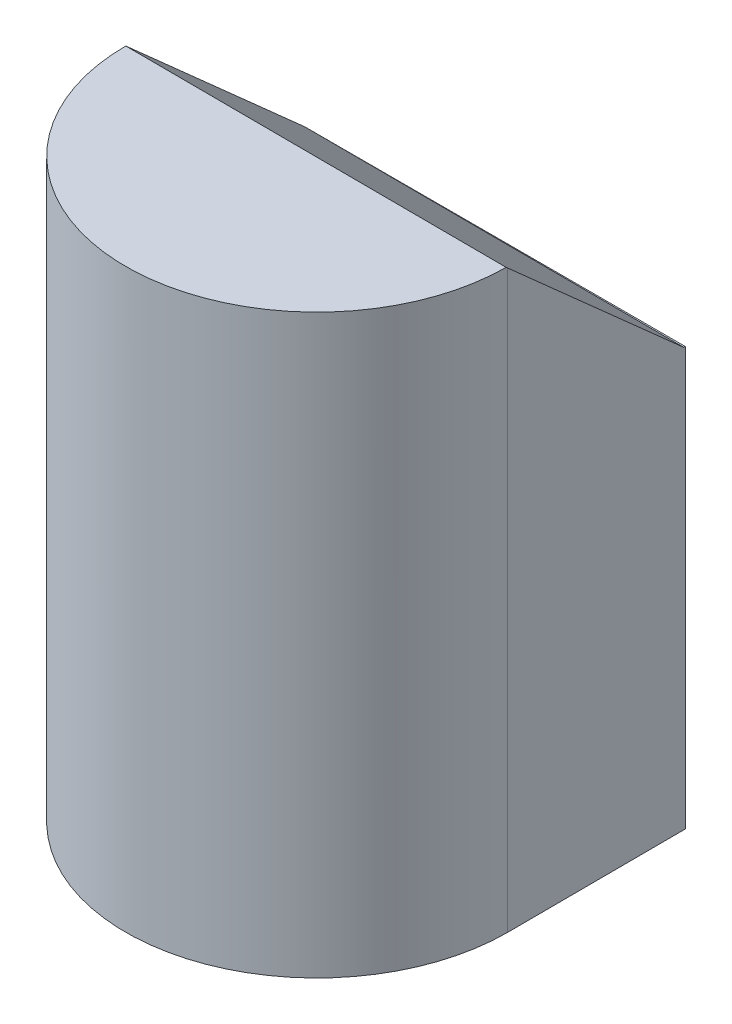
SolidWorks part; units mm, degrees
ref_plane "Front Plane" through (0, 0, 0) normal (0, 0, 1) x (1, 0, 0)
ref_plane "Top Plane" through (0, 0, 0) normal (0, 1, 0) x (1, 0, 0)
ref_plane "Right Plane" through (0, 0, 0) normal (1, 0, 0) x (0, 0, -1)
sketch "Sketch3" plane through (0, 0, 0) normal (0, 1, 0) x (1, 0, 0)
  line L1 (0, 0) -> (0, 270.6759) construction
  line L2 (-54.4068, 0) -> (54.4068, 0) construction
  line L3 (-54.4068, 0) -> (-54.2036, 50.8)
  line L4 (54.4068, 0) -> (54.2036, 50.8)
  line L5 (-54.2036, 50.8) -> (54.2036, 50.8)
  arc A0 (-54.4068, 0) -> (54.4068, 0) centre (0, 0) ccw
  point P7 (54.2036, 50.8)
  point P10 (-54.2036, 50.8)
  dimension "D1" = 108.8136
  dimension "D2" = 50.8
  dimension "D3" = 108.4072
extrude "Boss-Extrude1" add sketch "Sketch3" along normal blind 164.3062 contours L3 A0 L4 L5 region at (0, 0, -3.2151)
sketch "Sketch6" plane through (-54.4059, 0, -0.2176) normal (-1, 0, -0.004) x (-0.004, 0, 1)
  line L0 (0.2176, 164.3062) -> (-50.5828, 119.0752)
  line L1 (-50.5828, 164.3062) -> (-50.5828, 0) construction
  line L2 (0.2176, 164.3062) -> (-50.5828, 164.3062) construction
  line L3 (-50.5828, 164.3062) -> (-50.5828, 0)
  line L4 (0.2176, 164.3062) -> (-50.5828, 164.3062)
  line L5 (-50.5828, 119.0752) -> (-79.7411, 119.0752)
  line L6 (-79.7411, 119.0752) -> (-79.7411, 170.7432)
  line L7 (-79.7411, 170.7432) -> (0.2176, 170.7432)
  line L8 (0.2176, 170.7432) -> (0.2176, 164.3062)
  line M3 (0.2176, 164.3062) -> (-50.5828, 164.3062)
  line M4 (-50.5828, 164.3062) -> (-50.5828, 0)
  dimension "D1" = 119.0752
extrude "Cut-Extrude1" cut sketch "Sketch6" against normal through all contours L0 M3 M4 region at (-54.2713, 149.2292, -33.8667)
extrude "Cut-Extrude2" cut sketch "Sketch6<3>" against normal through all contours L0 M3 M4 | L8 L7 L6 L5 M4 M3 region at (-54.2713, 149.2292, -33.8667) region at (-54.1738, 148.9425, -58.2491)
sketch "Sketch6<3>" plane through (-54.4059, 0, -0.2176) normal (-1, 0, -0.004) x (-0.004, 0, 1) same geometry as "Sketch6"
sketch "Sketch10" plane through (0, 0, -50.8) normal (0, 0, -1) x (-1, 0, 0)
  line L0 (-54.2036, 119.0752) -> (-54.2036, 0) construction
  circle A0 centre (0, 59.5376) radius 23.7554
  point P0 (0, 59.5376)
  point P5 (-54.2036, 59.5376)
  dimension "D1" = 47.5107
extrude "Boss-Extrude2" [suppressed] add sketch "Sketch10" along normal blind 92.6211 contours A0
sketch "Sketch11" [suppressed] plane through (0, 0, -143.4211) normal (0, 0, -1) x (-1, 0, 0)
  circle A0 centre (0, 59.5376) radius 24.5491
  point P0 (0, 59.5376)
  dimension "D1" = 49.0982
extrude "Boss-Extrude3" [suppressed] add sketch "Sketch11" against normal blind 2.54 contours A0
sketch "Sketch12" plane through (54.4059, 0, -0.2176) normal (1, 0, -0.004) x (-0.004, 0, -1)
  line L0 (-54.4068, 164.3062) -> (-54.4068, 0) construction
  line L1 (0.2176, 164.3062) -> (51.0164, 119.0752) construction
  line L2 (0.2176, 164.3062) -> (-54.4068, 164.3062) construction
  line L3 (-54.4068, 164.3062) -> (-54.4068, 0)
  line L4 (0.2176, 164.3062) -> (51.0164, 119.0752)
  line L5 (0.2176, 164.3062) -> (-54.4068, 164.3062)
  line L10 (51.0164, 119.0752) -> (51.0164, 0) construction
  line L11 (-54.4068, 50.8) -> (-54.4068, 164.3062)
  line L12 (51.0164, 119.0752) -> (51.0164, 93.6752)
  line L13 (14.485, 106.3752) -> (-38.7394, 118.663)
  line L14 (-38.7394, 118.663) -> (-54.4068, 50.8)
  line L15 (14.485, 106.3752) -> (51.0164, 93.6752)
  line L16 (-54.4068, 0) -> (0, 0)
  line L17 (-54.4068, 50.8) -> (-54.4068, 0)
  line L18 (-54.4068, 25.4) -> (-54.4068, 0)
  arc A0 (-54.4068, 25.4) -> (0, 0) centre (0, 70.9697) ccw
  dimension "D5" = 25.4
  dimension "D1" = 13
  dimension "D2" = 50.8
  dimension "D3" = 25.4
  dimension "D4" = 12.7
extrude "Cut-Extrude4" [suppressed] cut sketch "Sketch12" against normal through all both
